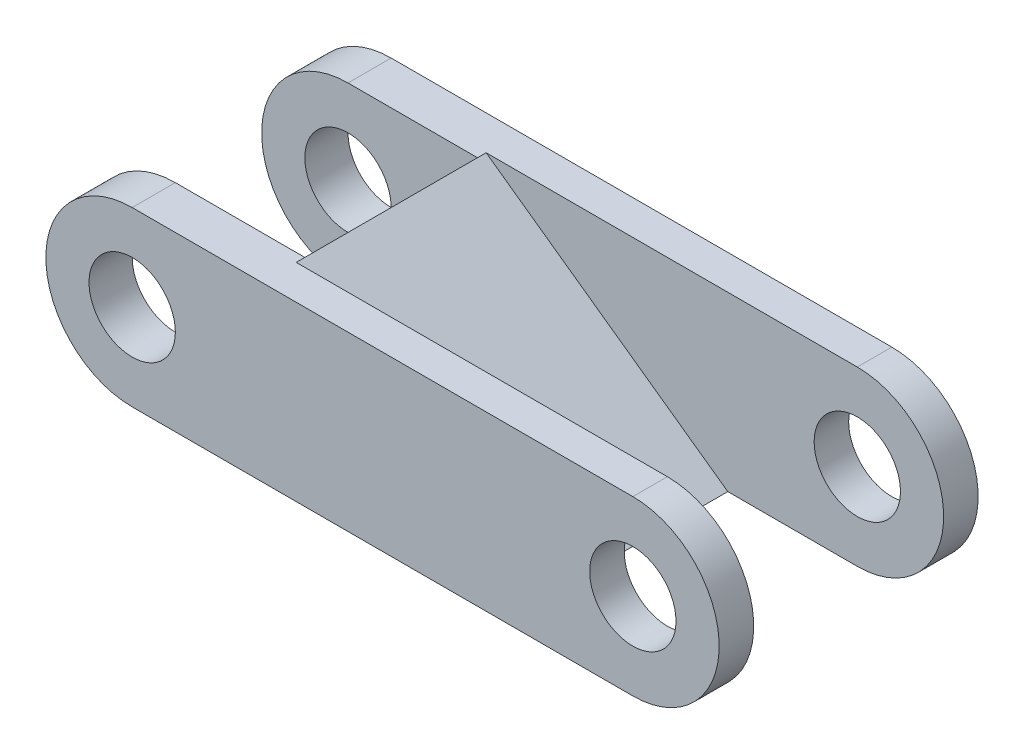
SolidWorks part; units mm, degrees
ref_plane "Front Plane" through (0, 0, 0) normal (0, 0, 1) x (1, 0, 0)
ref_plane "Top Plane" through (0, 0, 0) normal (0, 1, 0) x (1, 0, 0)
ref_plane "Right Plane" through (0, 0, 0) normal (1, 0, 0) x (0, 0, -1)
sketch "Sketch1" plane through (0, 0, 0) normal (0, 0, 1) x (1, 0, 0)
  line L0 (0, 0) -> (57.9939, 0) construction
  line L1 (0, 10) -> (57.9939, 10)
  line L2 (0, -10) -> (57.9939, -10)
  arc A0 (0, 10) -> (0, -10) centre (0, 0) ccw
  arc A1 (57.9939, -10) -> (57.9939, 10) centre (57.9939, 0) ccw
  circle A2 centre (0, 0) radius 5
  circle A3 centre (57.9939, 0) radius 5
  point P3 (28.9969, 0)
  dimension "D1" = 10
  dimension "D2" = 10
  dimension "D3" = 20
extrude "Boss-Extrude1" add sketch "Sketch1" along normal blind 30
sketch "Sketch2" plane through (0, 10, 0) normal (0, 1, 0) x (1, 0, 0)
  line L0 (-10, 0) -> (-10, -30) construction
  line L1 (15, -5) -> (-10, -5)
  line L2 (15, -5) -> (15, -25)
  line L3 (15, -25) -> (-10, -25)
  line L4 (-10, -5) -> (-10, -25)
  line L5 (67.9939, -30) -> (67.9939, 0) construction
  line L6 (0, -30) -> (0, 0) construction
  line L15 (42.9939, -26) -> (67.9939, -26)
  line L16 (42.9939, -26) -> (42.9939, -4)
  line L17 (42.9939, -4) -> (67.9939, -4)
  line L18 (67.9939, -26) -> (67.9939, -4)
  line L19 (57.9939, -30) -> (57.9939, 0) construction
  point P7 (-10, -15)
  point P10 (0, -15)
  point P15 (67.9939, -15)
  point P19 (57.9939, -15)
  dimension "D1" = 20
  dimension "D2" = 25
  dimension "D3" = 22
  dimension "D4" = 25
extrude "Cut-Extrude1" cut sketch "Sketch2" against normal through all
sketch "Sketch4" plane through (0, 0, 5) normal (0, 0, 1) x (1, 0, 0)
  line L0 (15, 10) -> (42.9939, 10)
  line L1 (42.9939, 10) -> (42.9939, -10)
  line L2 (42.9939, -10) -> (15, 10)
  point P3 (0, 0)
extrude "Cut-Extrude2" cut sketch "Sketch4" along normal up to surface (20 mm away) up to face at (5, 0, 25)
sketch "Sketch5" plane through (0, 0, 5) normal (0, 0, 1) x (1, 0, 0)
  line L3 (15, 10) -> (42.9939, -10)
  line L4 (42.9939, -10) -> (42.9939, 10)
  line L5 (42.9939, 10) -> (15, 10)
  line L6 (15, 10) -> (42.9939, -10)
  line L7 (42.9939, -10) -> (42.9939, 10)
  line L8 (42.9939, 10) -> (15, 10)
  dimension "D1" = 0
extrude "Cut-Extrude3" cut sketch "Sketch5" against normal up to surface and the other way up to surface up to face at (52.9939, 0, 4) other way up to face at (62.9939, 0, 26)
